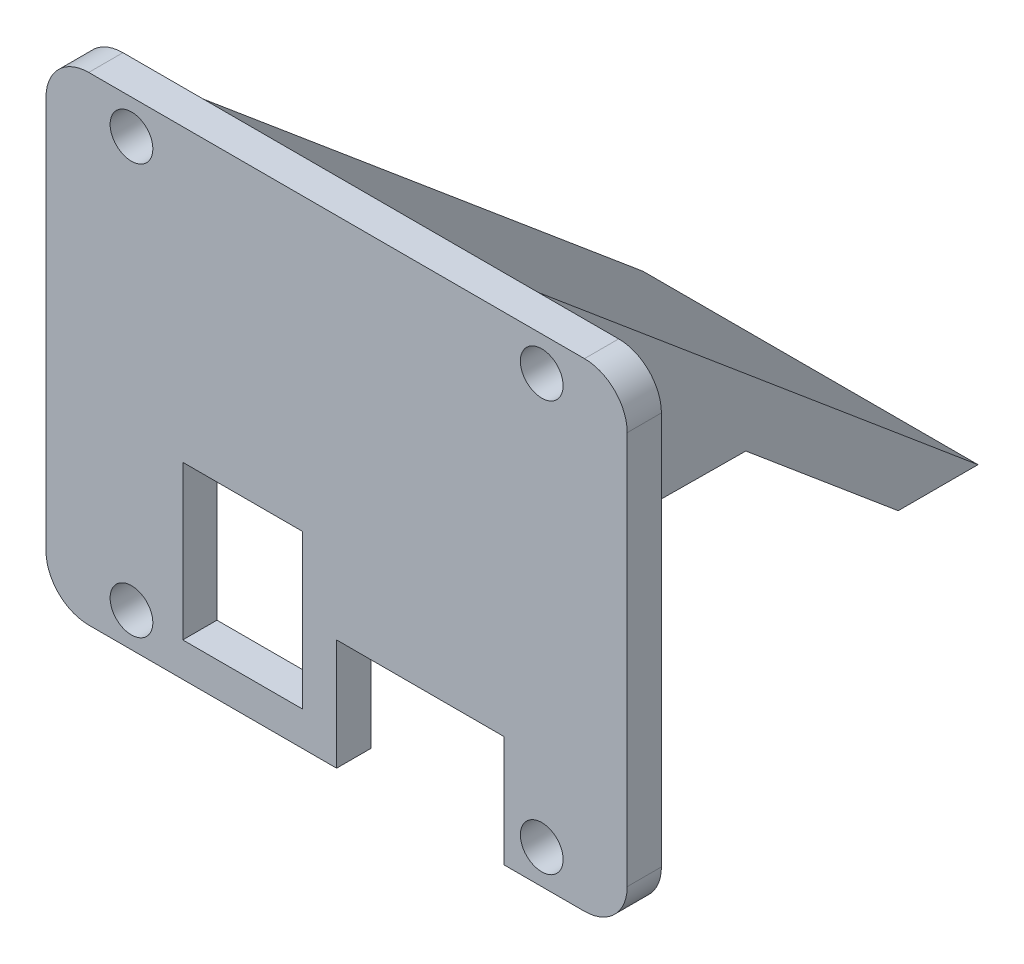
SolidWorks part; units mm, degrees
ref_plane "정면" through (0, 0, 0) normal (0, 0, 1) x (1, 0, 0)
ref_plane "윗면" through (0, 0, 0) normal (0, 1, 0) x (1, 0, 0)
ref_plane "우측면" through (0, 0, 0) normal (1, 0, 0) x (0, 0, -1)
sketch "스케치1" plane through (0, 0, 0) normal (0, 0, 1) x (1, 0, 0)
  line L1 (-11.5, 11.5) -> (11.5, 11.5)
  line L2 (-11.5, 11.5) -> (-11.5, -11.5)
  line L3 (-11.5, -11.5) -> (11.5, -11.5)
  line L4 (11.5, 11.5) -> (11.5, -11.5)
  line L5 (-11.5, 11.5) -> (11.5, -11.5) construction
  line L6 (-11.5, -11.5) -> (11.5, 11.5) construction
  line L7 (-20, 16) -> (20, 16)
  line L8 (-20, 16) -> (-20, -16)
  line L9 (-20, -16) -> (20, -16)
  line L10 (20, 16) -> (20, -16)
  line L11 (-20, 16) -> (20, -16) construction
  line L12 (-20, -16) -> (20, 16) construction
  circle A0 centre (-11.5, 11.5) radius 1.15
  circle A1 centre (11.5, 11.5) radius 1.15
  circle A2 centre (11.5, -11.5) radius 1.15
  circle A3 centre (-11.5, -11.5) radius 1.15
  point P0 (0, 0)
  point P10 (0, 0)
  dimension "D3" = 2.3
  dimension "D4" = 2.3
  dimension "D5" = 2.3
  dimension "D6" = 2.3
  dimension "D1" = 23
  dimension "D2" = 23
  dimension "D7" = 32
  dimension "D8" = 40
extrude "보스-돌출1" add sketch "스케치1" along normal blind 3 contours L10 L7 L8 L9 A3 L2 A0 L1 A1 L4 A2 L3 | A3 L3 A2 L4 A1 L1 A0 L2 region at (0, 0, 0) region at (0, 15.4878, 0)
sketch "스케치2" plane through (0, 0, 3) normal (0, 0, 1) x (1, 0, 0)
  line L0 (0, -16) -> (0, -14) construction
  line L1 (-20, -16) -> (20, -16) construction
  line L3 (0, -14) -> (9.8, -14)
  line L4 (0, -14) -> (0, -9)
  line L5 (0, -9) -> (9.8, -9)
  line L6 (9.8, -14) -> (9.8, -9)
  dimension "D1" = 2
  dimension "D2" = 9.8
  dimension "D3" = 5
extrude "컷-돌출1" cut sketch "스케치2" against normal blind 3
sketch "스케치3" plane through (0, 0, 3) normal (0, 0, 1) x (1, 0, 0)
  line L1 (-17, 14) -> (17, 14)
  line L2 (-17, 14) -> (-17, -14)
  line L3 (-17, -14) -> (17, -14)
  line L4 (17, 14) -> (17, -14)
  line L5 (-17, 14) -> (17, -14) construction
  line L6 (-17, -14) -> (17, 14) construction
  line L7 (-20, 16) -> (20, 16)
  line L8 (-20, 16) -> (-20, -16)
  line L9 (-20, -16) -> (20, -16)
  line L10 (20, 16) -> (20, -16)
  line L11 (-20, 16) -> (20, -16) construction
  line L12 (-20, -16) -> (20, 16) construction
  point P0 (0, 0)
  point P6 (0, 0)
  dimension "D1" = 34
  dimension "D2" = 28
extrude "컷-돌출2" cut sketch "스케치3" against normal blind 3
sketch "스케치4" plane through (0, 0, 3) normal (0, 0, 1) x (1, 0, 0)
  line L1 (-14, -11.5) -> (-14, -14)
  line L2 (-17, -14) -> (0, -14) construction
  line L3 (-14, -14) -> (-9, -14)
  line L4 (-9, -14) -> (-9, -11.5)
  line L5 (-14, -11.5) -> (-9, -11.5)
  line L6 (9.8, -14) -> (9.8, -9.667)
  line L7 (9.8, -14) -> (9.8, -9) construction
  line L8 (14, -11.5) -> (14, -14)
  line L9 (9.8, -14) -> (17, -14) construction
  line L10 (14, -14) -> (9.8, -14)
  line L11 (-14, 11.5) -> (-14, 14)
  line L12 (17, 14) -> (-17, 14) construction
  line L13 (-14, 14) -> (-9, 14)
  line L14 (-9, 14) -> (-9, 11.5)
  line L15 (-9, 11.5) -> (-14, 11.5)
  line L16 (9, 11.5) -> (9, 14)
  line L17 (9, 14) -> (14, 14)
  line L18 (14, 14) -> (14, 11.5)
  line L19 (14, 11.5) -> (9, 11.5)
  circle A0 centre (-11.5, 11.5) radius 2.5
  circle A1 centre (11.5, 11.5) radius 2.5
  circle A2 centre (11.5, -11.5) radius 2.5
  circle A3 centre (-11.5, -11.5) radius 2.5
  circle A4 centre (11.5, 11.5) radius 1.15
  circle A5 centre (11.5, -11.5) radius 1.15
  circle A6 centre (-11.5, -11.5) radius 1.15
  circle A7 centre (-11.5, 11.5) radius 1.15
  circle M3 centre (-11.5, 11.5) radius 1.15
  circle M4 centre (11.5, -11.5) radius 1.15
  circle M5 centre (11.5, 11.5) radius 1.15
  circle M6 centre (-11.5, -11.5) radius 1.15
  line M7 (9.8, -9) -> (9.8, -14)
extrude "보스-돌출2" add sketch "스케치4" along normal blind 1 contours L19 A1 M5 | L19 A1 M5 | L15 A0 M3 | L15 A0 M3 | L5 A3 M6 | L5 A3 M6 | A2 M7 M4 region at (-11.5, -10.2852, 3) region at (-11.5, -12.7148, 3) region at (9.8653, -11.5, 3) region at (-11.5, 12.7148, 3) region at (-11.5, 10.2852, 3) region at (11.5, 12.7148, 3) region at (11.5, 10.2852, 3)
sketch "스케치5" plane through (0, 0, 3) normal (0, 0, 1) x (1, 0, 0)
  line L0 (-11.5, -14) -> (0, -14) construction
  line L1 (-14, -11.5) -> (-9, -11.5)
  line L2 (-14, -11.5) -> (-14, -14)
  line L3 (-14, -14) -> (-9, -14)
  line L4 (-9, -11.5) -> (-9, -14)
  line L5 (9.8, -11.5) -> (14, -11.5)
  line L6 (9.8, -9.667) -> (9.8, -13.333) construction
  line L7 (14, -11.5) -> (14, -14)
  line L8 (11.5, -14) -> (17, -14) construction
  line L9 (14, -14) -> (9.8, -14)
  line L10 (9.8, -14) -> (9.8, -11.5)
  line L11 (17, 14) -> (11.5, 14) construction
  line L12 (9, 11.5) -> (14, 11.5)
  line L13 (9, 11.5) -> (9, 14)
  line L14 (9, 14) -> (14, 14)
  line L15 (14, 11.5) -> (14, 14)
  line L16 (-11.5, 14) -> (-17, 14) construction
  line L17 (-9, 11.5) -> (-14, 11.5)
  line L18 (-9, 11.5) -> (-9, 14)
  line L19 (-9, 14) -> (-14, 14)
  line L20 (-14, 11.5) -> (-14, 14)
  circle A0 centre (-11.5, -11.5) radius 2.5 construction
  circle A1 centre (-11.5, -11.5) radius 2.5 construction
  arc A2 (9.8, -13.333) -> (9.8, -9.667) centre (11.5, -11.5) ccw construction
  circle A3 centre (11.5, 11.5) radius 2.5 construction
  circle A4 centre (11.5, 11.5) radius 2.5 construction
  circle A5 centre (-11.5, 11.5) radius 2.5 construction
  circle A6 centre (-11.5, 11.5) radius 2.5 construction
  circle A7 centre (-11.5, 11.5) radius 1.15
  circle A8 centre (11.5, 11.5) radius 1.15
  circle A9 centre (11.5, -11.5) radius 1.15
  circle A10 centre (-11.5, -11.5) radius 1.15
  arc M2 (9.8, -9.667) -> (11.5, -14) centre (11.5, -11.5) cw
  line M3 (11.5, -14) -> (17, -14)
  line M5 (17, 14) -> (11.5, 14)
  circle M6 centre (11.5, 11.5) radius 2.5
  line M7 (11.5, 14) -> (-11.5, 14)
  circle M8 centre (-11.5, 11.5) radius 2.5
  line M9 (-11.5, 14) -> (-17, 14)
  line M11 (-17, -14) -> (-11.5, -14)
  circle M12 centre (-11.5, -11.5) radius 2.5
  line M13 (-11.5, -14) -> (0, -14)
extrude "보스-돌출3" add sketch "스케치5" along normal blind 1 contours L7 M2 M3 | L2 M12 M11 | L4 M12 M13 | L20 M8 M9 | L18 M8 M7 | L13 M6 M7 | L15 M6 M5 | A9 L5 L10 L9 M2 region at (-9.5584, -13.4416, 3) region at (-13.4416, -13.4416, 3) region at (11.7254, -12.8425, 3) region at (13.4416, -13.4416, 3) region at (13.4416, 13.4416, 3) region at (-9.5584, 13.4416, 3) region at (9.5584, 13.4416, 3) region at (-13.4416, 13.4416, 3)
sketch "스케치6" plane through (-17, 0, 0) normal (-1, 0, 0) x (0, 0, 1)
  line L0 (0, -14) -> (0, 21.9783)
  line L1 (0, 14) -> (-22.9813, -5.2836)
  line L2 (-11.4907, 4.3582) -> (-9.5623, 2.0601) construction
  line L3 (-22.9813, -5.2836) -> (-21.053, -7.5818) construction
  line L4 (-22.9813, -5.2836) -> (-21.053, -7.5818)
  line L5 (-21.053, -7.5818) -> (-9.5623, 2.0601)
  line L6 (-9.5623, 2.0601) -> (0, 10.0838)
  line L7 (0, 10.0838) -> (0, 14)
  line L8 (0, 0) -> (-12.1375, -0.1008)
  line L9 (-12.1375, -0.1008) -> (0, 10.0838)
  line L10 (0, 0) -> (0, 10.0838)
  line L11 (-21.053, -7.5818) -> (-26.8116, -8.4976)
  line L12 (-22.9813, -5.2836) -> (-26.8116, -8.4976)
  line L13 (-22.9813, -5.2836) -> (-21.053, -7.5818)
  line M7 (0, 14) -> (0, -14)
  dimension "D1" = 50
  dimension "D2" = 30
  dimension "D3" = 3
  dimension "D4" = 90
  dimension "D5" = 3
  dimension "D6" = 5
extrude "보스-돌출5" add sketch "스케치6" against normal up to vertex (26.8 mm away) contours L4 L12 L11 | L5 L6 L1 L4 M7 | L8 L0 L6 L5 region at (-17, 3.3277, -4.0458) region at (-17, 2.8273, -11.0156) region at (-17, -7.121, -23.6153) up to point (9.8, -9, 0)
sketch "스케치7" plane through (-17, 0, 0) normal (-1, 0, 0) x (0, 0, 1)
  line L8 (0, 0) -> (0, 14)
  line L9 (0, 14) -> (-26.8116, -8.4976)
  line L10 (-21.053, -7.5818) -> (-26.8116, -8.4976) construction
  line L11 (0, 14) -> (-26.8116, -8.4976) construction
  line L12 (-26.8116, -8.4976) -> (-21.053, -7.5818)
  line L13 (-21.053, -7.5818) -> (-12.1375, -0.1008)
  line L14 (-12.1375, -0.1008) -> (0, 0)
extrude "컷-돌출5" cut sketch "스케치7" against normal blind 7.2
sketch "스케치8" plane through (-9.8, 0, 0) normal (-1, 0, 0) x (0, 0, 1)
  line L1 (-21.053, -7.5818) -> (-28.0561, -7.5818)
  line L2 (-21.053, -7.5818) -> (-21.053, -10.0456)
  line L3 (-21.053, -10.0456) -> (-28.0561, -10.0456)
  line L4 (-28.0561, -7.5818) -> (-28.0561, -10.0456)
extrude "컷-돌출6" cut sketch "스케치8" against normal blind 20
sketch "스케치10" plane through (0, 0, 4) normal (0, 0, 1) x (1, 0, 0)
  line L1 (-17, -14) -> (17, -14)
  line L2 (-17, -14) -> (-17, 14)
  line L3 (-17, 14) -> (17, 14)
  line L4 (17, -14) -> (17, 14)
  line L5 (-17, -14) -> (17, 14) construction
  line L6 (-17, 14) -> (17, -14) construction
  line L7 (-14, 9) -> (-9, 9)
  line L8 (-14, 9) -> (-14, 14)
  line L9 (-14, 14) -> (-9, 14)
  line L10 (-9, 9) -> (-9, 14)
  line L11 (-14, 9) -> (-9, 14) construction
  line L12 (-14, 14) -> (-9, 9) construction
  line L13 (9, 9) -> (14, 9)
  line L14 (9, 9) -> (9, 14)
  line L15 (9, 14) -> (14, 14)
  line L16 (14, 9) -> (14, 14)
  line L17 (9, 9) -> (14, 14) construction
  line L18 (9, 14) -> (14, 9) construction
  line L19 (-14, -9) -> (-9, -9)
  line L20 (-14, -9) -> (-14, -14)
  line L21 (-14, -14) -> (-9, -14)
  line L22 (-9, -9) -> (-9, -14)
  line L23 (-14, -9) -> (-9, -14) construction
  line L24 (-14, -14) -> (-9, -9) construction
  line L25 (9.8, -14) -> (14, -14)
  line L26 (9.8, -14) -> (9.8, -9)
  line L27 (9.8, -9) -> (14, -9)
  line L28 (14, -14) -> (14, -9)
  point P0 (0, 0)
  point P7 (-11.5, 11.5)
  point P14 (11.5, 11.5)
  point P21 (-11.5, -11.5)
  circle M1 centre (-11.5, 11.5) radius 1.15
  arc M2 (-14, 11.5) -> (-9, 11.5) centre (-11.5, 11.5) ccw
  line M3 (-9, 11.5) -> (-9, 14)
  line M4 (-9, 14) -> (-14, 14)
  line M5 (-14, 14) -> (-14, 11.5)
extrude "컷-돌출7" cut sketch "스케치10" against normal up to vertex (1 mm away) contours M5 M2 M3 M4 M1 | L13 L16 L3 L14 | L1 L28 L27 L26 | L22 L19 L20 L1 region at (-11.5, -11.5, 4) region at (-11.5, 13.9293, 4) region at (11.9, -11.5, 4) region at (11.5, 11.5, 4) up to point (-17, 14, 3)
sketch "스케치11" plane through (0, 0, 3) normal (0, 0, 1) x (1, 0, 0)
  circle A0 centre (-11.5, 11.5) radius 1.15
  circle A1 centre (11.5, 11.5) radius 1.15
  circle A2 centre (11.5, -11.5) radius 1.15
  circle A3 centre (-11.5, -11.5) radius 1.15
extrude "보스-돌출6" add sketch "스케치11" against normal blind 3
sketch "스케치12" plane through (0, 0, 3) normal (0, 0, 1) x (1, 0, 0)
  line L1 (-12, -12) -> (12, -12)
  line L2 (-12, -12) -> (-12, 12)
  line L3 (-12, 12) -> (12, 12)
  line L4 (12, -12) -> (12, 12)
  line L5 (-12, -12) -> (12, 12) construction
  line L6 (-12, 12) -> (12, -12) construction
  circle A0 centre (-12, 12) radius 1.25
  circle A1 centre (12, 12) radius 1.25
  circle A2 centre (12, -12) radius 1.25
  circle A3 centre (-12, -12) radius 1.25
  point P0 (0, 0)
  dimension "D3" = 2.5
  dimension "D4" = 2.5
  dimension "D5" = 2.5
  dimension "D6" = 2.5
  dimension "D1" = 24
  dimension "D2" = 24
extrude "컷-돌출8" cut sketch "스케치12" against normal blind 10 contours L3 A0 L2 | L2 A0 L3 | L4 A1 L3 | L3 A1 L4 | L1 A2 L4 | L4 A2 L1 | L1 A3 L2 | L2 A3 L1 | A2 region at (-11.4695, -11.4695, 3) region at (-12.1768, -12.1768, 3) region at (11.4695, -11.4695, 3) region at (12.1768, -12.1768, 3) region at (-12.1768, 12.1768, 3) region at (-11.4695, 11.4695, 3) region at (11.4695, 11.4695, 3) region at (12.1768, 12.1768, 3)
sketch "스케치13" plane through (0, 0, 3) normal (0, 0, 1) x (1, 0, 0)
  line L0 (-14, -12) -> (-14, -14)
  line L1 (-17, -14) -> (0, -14) construction
  line L2 (-14, -14) -> (-10, -14)
  line L3 (-10, -14) -> (-10, -12)
  line L4 (10, -12) -> (10, -14)
  line L5 (9.8, -14) -> (17, -14) construction
  line L6 (10, -14) -> (14, -14)
  line L7 (14, -14) -> (14, -12)
  line L8 (10, 12) -> (10, 14)
  line L9 (17, 14) -> (-17, 14) construction
  line L10 (10, 14) -> (14, 14)
  line L11 (14, 14) -> (14, 12)
  line L12 (-14, 12) -> (-14, 14)
  line L13 (-14, 14) -> (-10, 14)
  line L14 (-10, 14) -> (-10, 12)
  circle A0 centre (-12, 12) radius 2
  circle A1 centre (12, 12) radius 2
  circle A2 centre (12, -12) radius 2
  circle A3 centre (-12, -12) radius 2
  circle A4 centre (-12, 12) radius 1.25
  circle A5 centre (-12, -12) radius 1.25
  circle A6 centre (12, -12) radius 1.25
  circle A7 centre (12, 12) radius 1.25
  circle M1 centre (-12, -12) radius 1.25
  circle M2 centre (12, -12) radius 1.25
  circle M3 centre (12, 12) radius 1.25
  circle M4 centre (-12, 12) radius 1.25
  line M7 (9.8, -14) -> (17, -14)
  line M9 (17, 14) -> (-17, 14)
  line M11 (-17, -14) -> (0, -14)
extrude "보스-돌출9" add sketch "스케치13" along normal blind 1 contours A1 L11 M9 | A1 L10 L8 | A1 M3 | A0 L14 M9 | A0 L13 L12 | A0 M4 | A3 M1 | A3 L2 L3 | A3 L0 M11 | A2 L6 L7 | A2 L4 M7 | A2 M2 region at (-13.5533, -13.5533, 3) region at (-12, -10.0566, 3) region at (-10.4467, -13.5533, 3) region at (10.4467, -13.5533, 3) region at (12, -10.0566, 3) region at (13.5533, -13.5533, 3) region at (-10.4467, 13.5533, 3) region at (10.6258, 13.3742, 3) region at (10.4467, 13.5533, 3) region at (13.5533, 13.5533, 3) region at (-13.5533, 13.5533, 3) region at (-10.6258, 13.3742, 3)
sketch "스케치14" plane through (0, 0, 3) normal (0, 0, 1) x (1, 0, 0)
  line L1 (17, -14) -> (-17, -14)
  line L2 (17, -14) -> (17, 14)
  line L3 (17, 14) -> (-17, 14)
  line L4 (-17, -14) -> (-17, 14)
  line L5 (16, -9.75) -> (-16, -9.75)
  line L6 (16, -9.75) -> (16, 9.75)
  line L7 (16, 9.75) -> (-16, 9.75)
  line L8 (-16, -9.75) -> (-16, 9.75)
  line L9 (16, -9.75) -> (-16, 9.75) construction
  line L10 (16, 9.75) -> (-16, -9.75) construction
  line L11 (0, -9.75) -> (-8, -9.75)
  line L12 (0, -9.75) -> (0, -12.75)
  line L13 (0, -12.75) -> (-8, -12.75)
  line L14 (-8, -9.75) -> (-8, -12.75)
  point P0 (0, 0)
  point P7 (0, 0)
  line M29 (0, -14) -> (0, -9)
  line M30 (0, -9) -> (9.8, -9)
  line M31 (9.8, -9) -> (9.8, -14)
  dimension "D1" = 32
  dimension "D2" = 19.5
  dimension "D3" = 8
  dimension "D4" = 3
extrude "컷-돌출10" cut sketch "스케치14" against normal blind 1.5 contours L8 L5 L6 L7 M29 M30 M31 | L5 L14 L13 M29 region at (-0.0584, 0.1117, 3) region at (-4, -11.25, 3)
fillet "필렛1" radius 2.5 4 edges at (-17, -14, 1.5) (17, -14, 1.5) (17, 14, 1.5) (-17, 14, 1.5)
sketch "스케치15" plane through (0, 0, 1.5) normal (0, 0, 1) x (1, 0, 0)
  line L1 (0, -9) -> (9.8, -9)
  line L2 (0, -9) -> (0, -7.5)
  line L3 (0, -7.5) -> (9.8, -7.5)
  line L4 (9.8, -9) -> (9.8, -7.5)
  dimension "D1" = 9.8
  dimension "D2" = 1.5
extrude "컷-돌출11" cut sketch "스케치15" against normal blind 10
sketch "스케치16" plane through (0, 0, 1.5) normal (0, 0, 1) x (1, 0, 0)
  line L20 (0, -12.75) -> (0, -7.5)
  line L21 (0, -7.5) -> (9.8, -7.5)
  line L22 (9.8, -7.5) -> (9.8, -9.75)
  line L23 (9.8, -9.75) -> (16, -9.75)
  line L24 (16, -9.75) -> (16, 9.75)
  line L25 (16, 9.75) -> (-16, 9.75)
  line L26 (-16, 9.75) -> (-16, -9.75)
  line L27 (-16, -9.75) -> (-8, -9.75)
  line L28 (-8, -9.75) -> (-8, -12.75)
  line L29 (-8, -12.75) -> (0, -12.75)
  line L30 (0, -12.75) -> (0, -7.5)
  line L31 (0, -7.5) -> (9.8, -7.5)
  line L32 (9.8, -7.5) -> (9.8, -9.75)
  line L33 (9.8, -9.75) -> (16, -9.75)
  line L34 (16, -9.75) -> (16, 9.75)
  line L35 (16, 9.75) -> (-16, 9.75)
  line L36 (-16, 9.75) -> (-16, -9.75)
  line L37 (-16, -9.75) -> (-8, -9.75)
  line L38 (-8, -9.75) -> (-8, -12.75)
  line L39 (-8, -12.75) -> (0, -12.75)
  dimension "D1" = 0
extrude "보스-돌출10" add sketch "스케치16" along normal up to vertex (1.5 mm away) contours L30 L31 L32 L33 L34 L35 L36 L37 L38 L39 up to point (0, -12.75, 3)
sketch "스케치17" plane through (0, 0, 3) normal (0, 0, 1) x (1, 0, 0)
  line L40 (0, -7.5) -> (9.8, -7.5)
  line L41 (9.8, -7.5) -> (9.8, -14)
  line L42 (9.8, -14) -> (10, -14)
  line L43 (10, -14) -> (10, -12)
  line L44 (14, -12) -> (14, -14)
  line L45 (14, -14) -> (14.5, -14)
  line L46 (17, -11.5) -> (17, 11.5)
  line L47 (14.5, 14) -> (14, 14)
  line L48 (14, 14) -> (14, 12)
  line L49 (10, 12) -> (10, 14)
  line L50 (10, 14) -> (-10, 14)
  line L51 (-10, 14) -> (-10, 12)
  line L52 (-14, 12) -> (-14, 14)
  line L53 (-14, 14) -> (-14.5, 14)
  line L54 (-17, 11.5) -> (-17, -11.5)
  line L55 (-14.5, -14) -> (-14, -14)
  line L56 (-14, -14) -> (-14, -12)
  line L57 (-10, -12) -> (-10, -14)
  line L58 (-10, -14) -> (0, -14)
  line L59 (0, -14) -> (0, -7.5)
  line L60 (0, -7.5) -> (9.8, -7.5)
  line L61 (9.8, -7.5) -> (9.8, -14)
  line L62 (9.8, -14) -> (10, -14)
  line L63 (10, -14) -> (10, -12)
  line L64 (14, -12) -> (14, -14)
  line L65 (14, -14) -> (14.5, -14)
  line L66 (17, -11.5) -> (17, 11.5)
  line L67 (14.5, 14) -> (14, 14)
  line L68 (14, 14) -> (14, 12)
  line L69 (10, 12) -> (10, 14)
  line L70 (10, 14) -> (-10, 14)
  line L71 (-10, 14) -> (-10, 12)
  line L72 (-14, 12) -> (-14, 14)
  line L73 (-14, 14) -> (-14.5, 14)
  line L74 (-17, 11.5) -> (-17, -11.5)
  line L75 (-14.5, -14) -> (-14, -14)
  line L76 (-14, -14) -> (-14, -12)
  line L77 (-10, -12) -> (-10, -14)
  line L78 (-10, -14) -> (0, -14)
  line L79 (0, -14) -> (0, -7.5)
  arc A16 (14, -12) -> (10, -12) centre (12, -12) ccw
  arc A17 (14.5, -14) -> (17, -11.5) centre (14.5, -11.5) ccw
  arc A18 (17, 11.5) -> (14.5, 14) centre (14.5, 11.5) ccw
  arc A19 (10, 12) -> (14, 12) centre (12, 12) ccw
  arc A20 (-14, 12) -> (-10, 12) centre (-12, 12) ccw
  arc A21 (-14.5, 14) -> (-17, 11.5) centre (-14.5, 11.5) ccw
  arc A22 (-17, -11.5) -> (-14.5, -14) centre (-14.5, -11.5) ccw
  arc A23 (-10, -12) -> (-14, -12) centre (-12, -12) ccw
  arc A24 (14, -12) -> (10, -12) centre (12, -12) ccw
  arc A25 (14.5, -14) -> (17, -11.5) centre (14.5, -11.5) ccw
  arc A26 (17, 11.5) -> (14.5, 14) centre (14.5, 11.5) ccw
  arc A27 (10, 12) -> (14, 12) centre (12, 12) ccw
  arc A28 (-14, 12) -> (-10, 12) centre (-12, 12) ccw
  arc A29 (-14.5, 14) -> (-17, 11.5) centre (-14.5, 11.5) ccw
  arc A30 (-17, -11.5) -> (-14.5, -14) centre (-14.5, -11.5) ccw
  arc A31 (-10, -12) -> (-14, -12) centre (-12, -12) ccw
  dimension "D1" = 0
extrude "보스-돌출11" add sketch "스케치17" along normal up to vertex (1 mm away) up to point (-14, 14, 4)
sketch "스케치18" plane through (0, 0, 4) normal (0, 0, 1) x (1, 0, 0)
  line L1 (18.2508, -14.5026) -> (-18.2508, -14.5026)
  line L2 (18.2508, -14.5026) -> (18.2508, 14.5026)
  line L3 (18.2508, 14.5026) -> (-18.2508, 14.5026)
  line L4 (-18.2508, -14.5026) -> (-18.2508, 14.5026)
  line L5 (18.2508, -14.5026) -> (-18.2508, 14.5026) construction
  line L6 (18.2508, 14.5026) -> (-18.2508, -14.5026) construction
  point P0 (0, 0)
extrude "컷-돌출12" cut sketch "스케치18" against normal blind 2
sketch "스케치19" plane through (0, 0, 2) normal (0, 0, 1) x (1, 0, 0)
  line L0 (0, -7.5) -> (-5.5, -7.5) construction
  line L2 (-2, -12) -> (-9, -12)
  line L3 (-2, -12) -> (-2, -3)
  line L4 (-2, -3) -> (-9, -3)
  line L5 (-9, -12) -> (-9, -3)
  line L6 (-2, -12) -> (-9, -3) construction
  line L7 (-2, -3) -> (-9, -12) construction
  dimension "D1" = 5.5
  dimension "D2" = 7
  dimension "D3" = 9
extrude "컷-돌출13" cut sketch "스케치19" against normal blind 2
